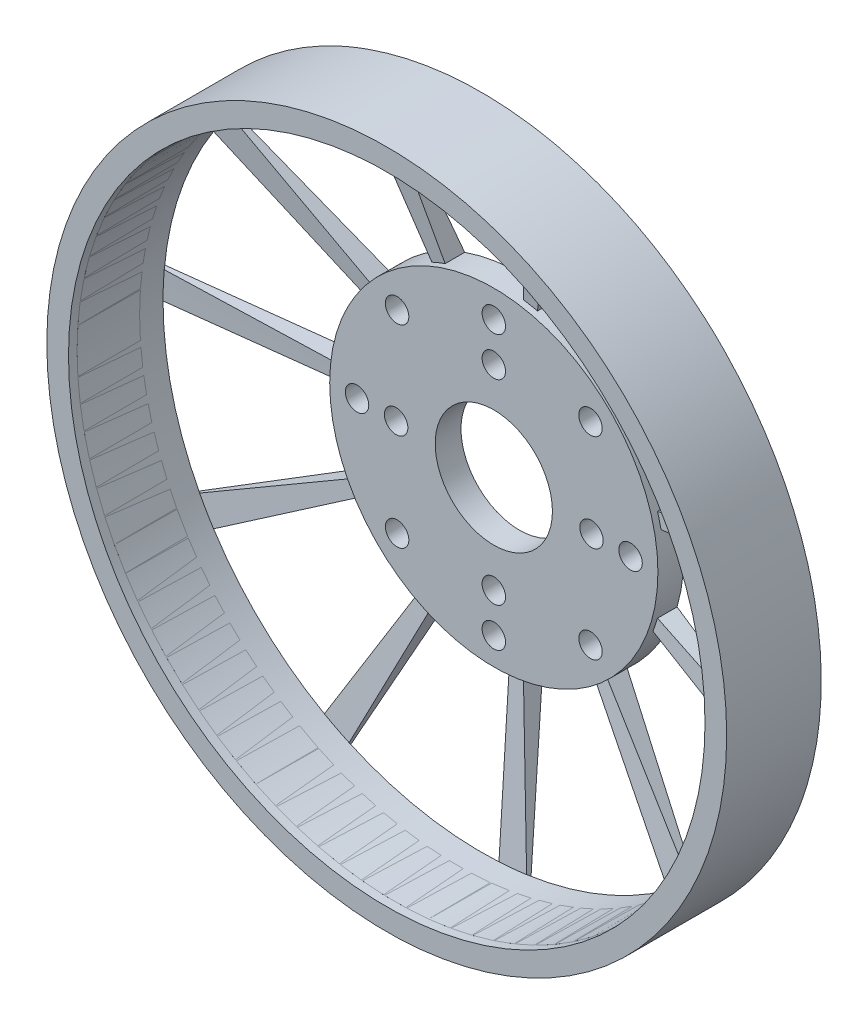
SolidWorks part; units mm, degrees
ref_plane "Front Plane" through (0, 0, 0) normal (0, 0, 1) x (1, 0, 0)
ref_plane "Top Plane" through (0, 0, 0) normal (0, 1, 0) x (1, 0, 0)
ref_plane "Right Plane" through (0, 0, 0) normal (1, 0, 0) x (0, 0, -1)
sketch "Sketch1" plane through (0, 0, 0) normal (0, 0, 1) x (1, 0, 0)
  circle A0 centre (0, 0) radius 40.725
  circle A1 centre (0, 0) radius 43.5
  circle A2 centre (0, 0) radius 21
  circle A3 centre (0, 0) radius 7.5
  circle A4 centre (0, 0) radius 7.5
  dimension "D1" = 81.45
  dimension "D2" = 87
  dimension "D3" = 42
  dimension "D4" = 15
  dimension "D5" = 15
extrude "Boss-Extrude1" add sketch "Sketch1" along normal blind 12.1 from offset 4.9 contours A1 A0 region at (-42.2696, 0, 0)
extrude "Boss-Extrude2" add sketch "Sketch1<4>" along normal blind 3.3 separate body contours A2 A3 region at (-20.406, 0, 0)
sketch "Sketch1<4>" plane through (0, 0, 0) normal (0, 0, 1) x (1, 0, 0) same geometry as "Sketch1"
sketch "Sketch2" plane through (0, 0, 0) normal (0, 1, 0) x (1, 0, 0)
  line L0 (21, 0) -> (-21, 0) construction
  line L1 (43.5, -4.9) -> (-43.5, -4.9) construction
  line L2 (21, 0) -> (-21, 0)
  line L3 (43.5, -4.9) -> (-43.5, -4.9)
  line L4 (-43.5, -4.9) -> (-21, 0)
  line L5 (-21, 0) -> (-21, -3.3) construction
  line L6 (40.725, -4.9) -> (-40.725, -4.9) construction
  line L7 (-21, 0) -> (-21, -3.3)
  line L8 (40.725, -4.9) -> (-40.725, -4.9)
  line L9 (-40.725, -4.9) -> (-21, -2.5)
  dimension "D1" = 2.5
ref_axis "Axis1" through (0, 0, 3.3) along (0, 0, -1)
revolve "Revolve1" add sketch "Sketch2" angle 5 about axis through (0, 0, 3.3) along (0, 0, -1) region at (-29.1961, 0, 2.6396)
pattern_circular "CirPattern1" count 11 over 360 about axis through (0, 0, 3.3) along (0, 0, -1) of "Revolve1" reverse direction yes
sketch "Sketch3" plane through (0, 0, 3.3) normal (0, 0, 1) x (1, 0, 0)
  circle A0 centre (0, 0) radius 7.5
  circle A1 centre (0, 0) radius 3.5
  dimension "D1" = 15
  dimension "D2" = 7
sketch "Sketch4" plane through (0, 0, 3.3) normal (0, 0, 1) x (1, 0, 0)
  circle A0 centre (0, 0) radius 8.25
  circle A1 centre (0, 0) radius 3.5
  circle A2 centre (0, 0) radius 7.5 construction
  circle A3 centre (0, 0) radius 7.5
  circle M5 centre (0, 0) radius 7.5
  dimension "D1" = 16.5
sketch "Sketch6" plane through (0, 0, 0) normal (0, 0, -1) x (-1, 0, 0)
  circle A0 centre (0, 0) radius 17.5 construction
  circle A1 centre (0, 0) radius 12.5 construction
  circle A2 centre (0, 12.5) radius 1.5
  circle A3 centre (12.5, 0) radius 1.5
  circle A4 centre (0, -12.5) radius 1.5
  circle A5 centre (-12.5, 0) radius 1.5
  circle A6 centre (0, 17.5) radius 1.5
  circle A7 centre (12.3744, 12.3744) radius 1.5
  circle A8 centre (17.5, 0) radius 1.5
  circle A9 centre (12.3744, -12.3744) radius 1.5
  circle A10 centre (0, -17.5) radius 1.5
  circle A11 centre (-12.3744, -12.3744) radius 1.5
  circle A12 centre (-17.5, 0) radius 1.5
  circle A13 centre (-12.3744, 12.3744) radius 1.5
  point P15 (0, 0)
  point P31 (0, 0)
  dimension "D1" = 35
  dimension "D2" = 25
  dimension "D3" = 3
  dimension "D5" = 3
  dimension "D4" = 4
  dimension "D6" = 8
extrude "Cut-Extrude1" cut sketch "Sketch6" against normal blind 5
sketch "Sketch7" plane through (0, 0, 17) normal (0, 0, 1) x (1, 0, 0)
  circle A0 centre (0, 0) radius 40.725
  circle A1 centre (0, 0) radius 43.25
  dimension "D1" = 86.5
extrude "Boss-Extrude5" add sketch "Sketch7" against normal blind 8 from offset 1.1 separate body offset against normal yes
extrude "Boss-Extrude6" [suppressed] add sketch "Sketch4" along normal blind 5.12 contours A0 M5
